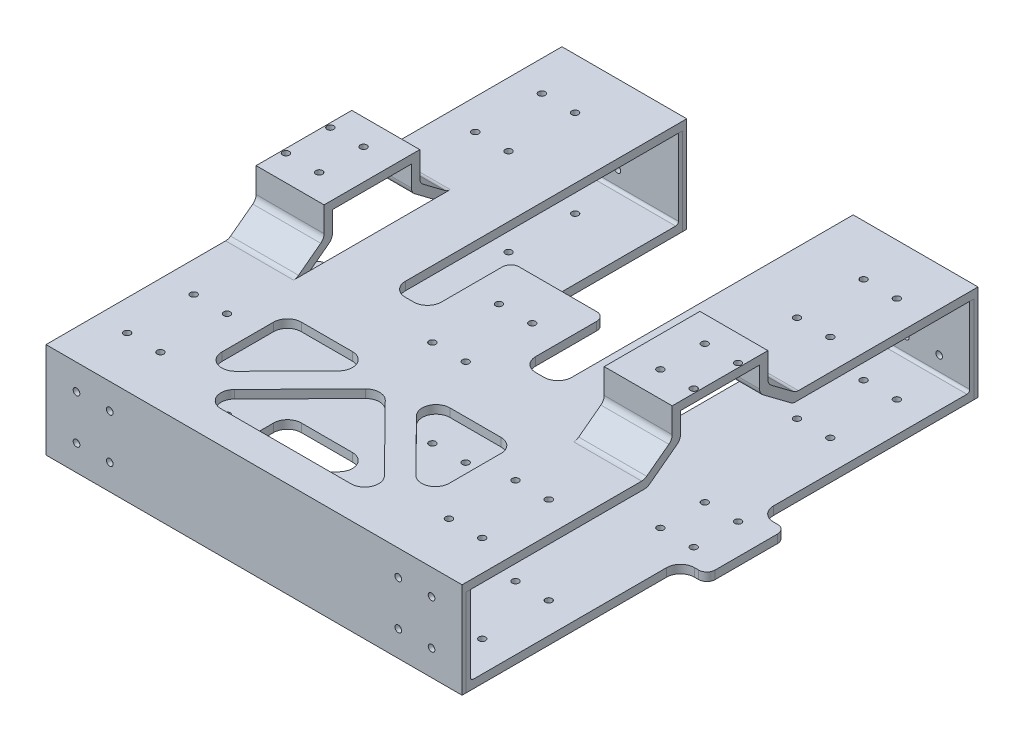
SolidWorks part; units mm, degrees
note: The reader was unsure of these and kept them because the rebuilt part matched: shared geometry of "Sketch14<6>".
ref_plane "Front" through (0, 0, 0) normal (0, 0, 1) x (1, 0, 0)
ref_plane "Top" through (0, 0, 0) normal (0, 1, 0) x (1, 0, 0)
ref_plane "Right" through (0, 0, 0) normal (1, 0, 0) x (0, 0, -1)
sketch "Top Layout" plane through (0, 0, 0) normal (0, 1, 0) x (1, 0, 0)
  line L0 (50.5, 0) -> (0, 0) construction
  line L5 (58, 43.5) -> (58, -43.5) construction
  line L6 (41, -78.75) -> (84, -78.75) construction
  line L25 (50.5, 0) -> (93.5, 0) construction
  line L26 (93.5, 50) -> (93.5, -50) construction
  line L27 (84, -28.75) -> (84, -128.75) construction
  line L31 (41, 78.75) -> (84, 78.75) construction
  line L32 (84, 128.75) -> (84, 28.75) construction
  point P0 (0, 0)
  point P6 (59.2, -42.4)
  point P8 (63.375, -50.8)
  point P9 (0, 0)
  point P16 (0, 0)
  point P24 (0, 0)
  point P25 (0, 0)
  point P26 (0, 0)
  line B0 (-6, -22.6978) -> (-6, 1.3022) construction
  line B1 (-17, -29.9478) -> (-17, 16.5522) construction
  line B2 (-17, -29.9478) -> (17, -29.9478) construction
  line B3 (17, -29.9478) -> (17, 16.5522) construction
  line B4 (-17, 16.5522) -> (17, 16.5522) construction
  line B5 (-6, 1.3022) -> (6, 1.3022) construction
  line B6 (6, 1.3022) -> (6, -22.6978) construction
  line B7 (6, -22.6978) -> (-6, -22.6978) construction
  line B8 (0, -22.6978) -> (0, -29.9478) construction
  line B9 (17, 5.3022) -> (-19, 5.3022) construction
  line B10 (75, -43.5) -> (41, -43.5) construction
  line B11 (75, -43.5) -> (75, -90) construction
  line B12 (75, -90) -> (41, -90) construction
  line B13 (41, -43.5) -> (41, -90) construction
  line B14 (58, -78.75) -> (58, -90) construction
  dimension "D2" = 75
  dimension "D5" = 90
  dimension "D7" = 9
  dimension "D8" = 100
  dimension "D9" = 90
  dimension "D10" = 9.5
sketch_block_instance "DYNAMIXEL 430 TopBot-1"
sketch_block "DYNAMIXEL 430 TopBot" parameters "D1"=28.5, "D2"=34, "D3"=20.267, "D4"=13.9544, "D5"=12.6443, "D6"=6.0635
sketch_block_instance "Flat 430 Block-1"
sketch_block "Flat 430 Block" parameters "D1"=46.5, "D2"=34, "D3"=11.25, "D4"=6.2771, "D5"=20.8671, "D6"=8.1058, "D7"=13.2568
sketch_block_instance "DYNAMIXEL 430 Side-1"
sketch_block "DYNAMIXEL 430 Side" parameters "D1"=34, "D2"=46.5, "D3"=12, "D4"=24, "D5"=11.25, "D6"=2, "D7"=4
sketch_block_instance "Block2-1"
sketch_block "Block2" parameters "D1"=12, "D2"=11, "D3"=4, "D4"=24, "D5"=13.103, "D6"=44.647, "D7"=34
sketch "Sketch3" plane through (0, 0, 0) normal (0, 1, 0) x (1, 0, 0)
  line L1 (-88.9, -102.9045) -> (88.9, -102.9045)
  line L2 (-88.9, -102.9045) -> (-88.9, 102.9045)
  line L3 (-88.9, 102.9045) -> (88.9, 102.9045)
  line L4 (88.9, -102.9045) -> (88.9, 102.9045)
  line L5 (-88.9, -102.9045) -> (88.9, 102.9045) construction
  line L6 (-88.9, 102.9045) -> (88.9, -102.9045) construction
  point P0 (0, 0)
sketch "Sketch4" plane through (0, 0, 0) normal (1, 0, 0) x (0, 0, -1)
  line L0 (-90, 28.5) -> (-90, 0)
  line L1 (-90, 0) -> (90, 0)
  line L2 (90, 0) -> (90, 28.5)
  line L3 (90, 28.5) -> (91.5, 28.5)
  line L4 (91.5, 28.5) -> (91.5, -3)
  line L5 (91.5, -3) -> (-91.5, -3)
  line L6 (-91.5, -3) -> (-91.5, 28.5)
  line L7 (-91.5, 28.5) -> (-90, 28.5)
  point P11 (0, 0)
  point P13 (0, 0)
  point P16 (88.9, 28.5)
  point P17 (-91.9, -3)
  point P18 (-91.9, 28.5)
  point P19 (-91.9, -3)
  point P20 (0, 0)
  line B0 (-90, 14.25) -> (-78.75, 14.25) construction
  line B1 (-43.5, 0) -> (-90, 0) construction
  line B2 (-43.5, 0) -> (-43.5, 28.5) construction
  line B3 (-43.5, 28.5) -> (-90, 28.5) construction
  line B4 (-90, 0) -> (-90, 28.5) construction
  line B5 (90, 14.25) -> (78.75, 14.25) construction
  line B6 (43.5, 28.5) -> (90, 28.5) construction
  line B7 (43.5, 28.5) -> (43.5, 0) construction
  line B8 (43.5, 0) -> (90, 0) construction
  line B9 (90, 28.5) -> (90, 0) construction
  dimension "D1" = 1.5
  dimension "D2" = 3
sketch_block_instance "DYNAMIXEL 430 Front-1"
sketch_block "DYNAMIXEL 430 Front" parameters "D1"=46.5, "D2"=28.5, "D3"=11.25, "D4"=8, "D5"=8, "D6"=11, "D7"=11
sketch_block_instance "DYNAMIXEL 430 Front-3"
extrude "Boss-Extrude1" add sketch "Sketch4" along direction (1, 0, 0) on the side of the normal up to vertex (84.5 mm away) contours L7 L6 L5 L4 L3 L2 L1 L0
ref_plane "Plane1" through (50.5, 0, 0) normal (1, 0, 0) x (0, 0, -1)
sketch "Sketch14" plane through (50.5, 0, 0) normal (1, 0, 0) x (0, 0, -1)
  line L0 (-91.5, -3) -> (-91.5, 28.5)
  line L1 (-91.5, 28.5) -> (-26.25, 28.5)
  line L2 (91.5, 28.5) -> (91.5, -3)
  line L3 (91.5, -3) -> (93, -3)
  line L4 (93, -3) -> (93, 31.5)
  line L5 (93, 31.5) -> (27.25, 31.5)
  line L6 (-93, 31.5) -> (-93, -3)
  line L7 (-93, -3) -> (-91.5, -3)
  line L9 (-17.25, 49.5) -> (17.25, 49.5)
  line L10 (-27.25, 31.5) -> (-93, 31.5)
  line L12 (-14.25, 46.5) -> (14.25, 46.5)
  line L13 (0, 50) -> (0, -50) construction
  line L16 (26.25, 28.5) -> (91.5, 28.5)
  line L17 (-27.25, 31.5) -> (27.25, 31.5)
  line L18 (-26.25, 28.5) -> (26.25, 28.5)
  line L19 (-14.25, 46.5) -> (-14.25, 37.5)
  line L20 (-14.25, 37.5) -> (-26.25, 28.5)
  line L21 (-27.25, 31.5) -> (-17.25, 39)
  line L22 (-17.25, 39) -> (-17.25, 49.5)
  line L23 (-14.25, 46.5) -> (-14.25, 49.5) construction
  line L24 (-14.25, 46.5) -> (-17.25, 46.5) construction
  line L25 (-22.2922, 35.2183) -> (-20.4922, 32.8183) construction
  line L26 (14.25, 46.5) -> (14.25, 37.5)
  line L27 (17.25, 39) -> (17.25, 49.5)
  line L28 (27.25, 31.5) -> (17.25, 39)
  line L29 (14.25, 37.5) -> (26.25, 28.5)
  point P10 (-17.6072, 39.8035)
  point P26 (-21.5122, 37.3791)
  point P30 (0, 46.5)
  point P31 (0, 49.5)
  point P35 (-28.2297, 31.5)
  line B0 (0, 0) -> (0, 11.25) construction
  line B1 (14.25, 46.5) -> (14.25, 0) construction
  line B2 (14.25, 46.5) -> (-14.25, 46.5) construction
  line B3 (-14.25, 46.5) -> (-14.25, 0) construction
  line B4 (14.25, 0) -> (-14.25, 0) construction
  dimension "D1" = 1.5
  dimension "D2" = 3
  dimension "D3" = 3
  dimension "D4" = 9
  dimension "D5" = 12
sketch_block_instance "DYNAMIXEL 430 Front-4"
sketch_block "DYNAMIXEL 430 Front" parameters "D1"=46.5, "D2"=28.5, "D3"=11.25, "D4"=8, "D5"=8, "D6"=11, "D7"=11
extrude "Boss-Extrude2" add sketch "Sketch14" along normal blind 34 separate body
sketch "Sketch7" plane through (0, -3, 0) normal (0, -1, 0) x (1, 0, 0)
  line L0 (84.5, -14.25) -> (75, -14.25)
  line L1 (50.5, -14.25) -> (84.5, -14.25) construction
  line L2 (75, -14.25) -> (75, -93)
  line L4 (75, -93) -> (84.5, -93)
  line L5 (84.5, -93) -> (84.5, -14.25)
  line L7 (84.5, 14.25) -> (75, 14.25)
  line L8 (84.5, 14.25) -> (84.5, 93)
  line L9 (84.5, 93) -> (75, 93)
  line L10 (75, 14.25) -> (75, 93)
  line L11 (75, -90) -> (75, -43.5) construction
  line L17 (0, -93) -> (30, -93)
  line L18 (30, -93) -> (30, 13.4478)
  line L19 (30, 13.4478) -> (17, 13.4478)
  line L20 (17, 29.9478) -> (17, -16.5522) construction
  line L21 (17, 13.4478) -> (17, -16.5522)
  line L22 (17, -16.5522) -> (0, -16.5522)
  line L23 (-17, -16.5522) -> (17, -16.5522) construction
  line L24 (0, -16.5522) -> (0, -93)
  line L25 (84.5, -93) -> (50.5, -93) construction
  line L26 (84.5, 93) -> (50.5, 93) construction
  line L27 (84.5, 93) -> (84.5, 91.5) construction
  dimension "D1" = 30
  dimension "D2" = 30
extrude "Boss-Extrude4" add sketch "Sketch14<6>" against normal up to surface (50.5 mm away) up to face at (0, 13.5, 0)
sketch "Sketch14<6>" plane through (50.5, 0, 0) normal (1, 0, 0) x (0, 0, -1) same geometry as "Sketch14"
extrude "Cut-Extrude1" cut sketch "Sketch7" against normal through all
sketch "Sketch16" plane through (0, 49.5, 0) normal (0, 1, 0) x (1, 0, 0)
  line L1 (84.5, 14.25) -> (75, 14.25)
  line L2 (84.5, 14.25) -> (84.5, -14.25)
  line L3 (84.5, -14.25) -> (75, -14.25)
  line L4 (75, 14.25) -> (75, -14.25)
extrude "Cut-Extrude2" cut sketch "Sketch16" against normal up to next (3 mm away)
hole_wizard "M2 Clearance Hole4" positions "Sketch12" profile "Sketch13" hole size "M2" standard "ANSI Metric" end condition through all
sketch "Sketch12" plane through (0, -3, 0) normal (0, 1, 0) x (1, 0, 0)
  point P0 (52, -74.75)
  point P3 (64, -74.75)
  point P6 (64, -50.75)
  point P9 (52, -50.75)
  point P12 (73.5, -8)
  point P15 (73.5, 8)
  point P18 (64, 74.75)
  point P21 (52, 74.75)
  point P24 (52, 50.75)
  point P27 (64, 50.75)
  point P30 (6, -22.6978)
  point P32 (6, 1.3022)
  point P34 (61.5, -8)
  point P36 (61.5, 8)
sketch "Sketch13" plane through (52, -3, 74.75) normal (1, 0, 0) x (0, 0, -1)
  line L0 (0, 0) -> (0, 52.5)
  line L1 (0, 52.5) -> (1.2, 52.5)
  line L2 (1.2, 52.5) -> (1.2, 0)
  line L5 (1.2, 0) -> (0, 0)
  line L11 (0, -6.35) -> (0, 107.95) construction
  dimension "Thru Hole Dia." = 2.4
  dimension "Thru Hole Depth" = 52.5
hole_wizard "M2 Clearance Hole5" positions "Sketch17" profile "Sketch18" hole size "M2" standard "ANSI Metric" end condition through all
sketch "Sketch17" plane through (0, 0, 93) normal (0, 0, 1) x (1, 0, 0)
  line L0 (41, 0) -> (84, 0) construction
  point P16 (52, 6.25)
  point P18 (64, 6.25)
  point P20 (64, 22.25)
  point P22 (52, 22.25)
  line B0 (41, 28.5) -> (75, 28.5) construction
sketch_block_instance "Block4-1"
sketch_block "Block4" parameters "D1"=28.5, "D2"=34, "D3"=20.267, "D4"=13.9544, "D5"=12.6443, "D6"=6.0635
sketch "Sketch18" plane through (52, 22.25, 93) normal (1, 0, 0) x (0, -1, 0)
  line L0 (0, 0) -> (0, 186)
  line L1 (0, 186) -> (1.2, 186)
  line L2 (1.2, 186) -> (1.2, 0)
  line L5 (1.2, 0) -> (0, 0)
  line L11 (0, -6.35) -> (0, 107.95) construction
  dimension "Thru Hole Dia." = 2.4
  dimension "Thru Hole Depth" = 186
mirror "Mirror1" about plane through (0, 0, 0) normal (1, 0, 0) of bodies 117 118 106 112
sketch "Sketch19" plane through (0, -3, 0) normal (0, -1, 0) x (1, 0, 0)
  line L0 (41, 43.5) -> (41, 90) construction
  line L1 (-41, 81.5) -> (41, 81.5)
  line L2 (-41, 81.5) -> (-41, 39.9478)
  line L3 (-41, 39.9478) -> (41, 39.9478)
  line L4 (41, 81.5) -> (41, 39.9478)
  line L5 (0, 0) -> (0, 81.5) construction
  line L6 (75, 91.5) -> (-75, 91.5) construction
  line L7 (-17, 29.9478) -> (17, 29.9478) construction
  line L8 (41, 81.5) -> (0, 39.9478) construction
  line L9 (0, 39.9478) -> (-41, 81.5) construction
  line L10 (38.1527, 84.3094) -> (0, 45.6429)
  line L11 (0, 45.6429) -> (-38.1527, 84.3094)
  line L12 (43.8473, 78.6906) -> (0, 34.2527)
  line L13 (0, 34.2527) -> (-43.8473, 78.6906)
  dimension "D1" = 10
  dimension "D2" = 10
  dimension "D3" = 4
  dimension "D4" = 4
extrude "Cut-Extrude3" cut sketch "Sketch19" against normal through all contours L4 L12 L3 | L11 L10 L1 | L3 L13 L2
fillet "Fillet1" radius 5 17 edges at (75, -1.5, 14.25) (75, -1.5, -14.25) (30, -1.5, 13.4478) (17, -1.5, 13.4478) (-17, -1.5, 13.4478) (-30, -1.5, 13.4478) (-75, -1.5, 14.25) (-75, -1.5, -14.25) (5.6194, -1.5, 39.9478) (41, -1.5, 75.8049) (41, -1.5, 39.9478) (0, -1.5, 45.6429) (-35.3806, -1.5, 81.5) (-41, -1.5, 39.9478) (-41, -1.5, 75.8049) (-5.6194, -1.5, 39.9478) (35.3806, -1.5, 81.5)
fillet "Fillet2" radius 3 5 edges at (-84.5, -1.5, -14.25) (-84.5, -1.5, 14.25) (84.5, -1.5, 14.25) (84.5, -1.5, -14.25) (-17, -1.5, -16.5522)
fillet "Fillet3" radius 1 3 edges at (-52.5, 0, -90) (52.5, 0, -90) (0, 0, 90)
fillet "Fillet5" radius 3 18 edges at (62.75, 28.5, -26.25) (62.75, 28.5, 26.25) (62.75, 31.5, 27.25) (62.75, 31.5, -27.25) (62.75, 39, 17.25) (62.75, 39, -17.25) (62.75, 37.5, -14.25) (62.75, 37.5, 14.25) (17, 30, -16.5522) (-62.75, 37.5, 14.25) (-62.75, 37.5, -14.25) (-62.75, 28.5, -26.25) (-62.75, 39, -17.25) (-62.75, 39, 17.25) (-62.75, 31.5, 27.25) (-62.75, 31.5, -27.25) (-62.75, 28.5, 26.25) (-17, 30, -16.5522)
fillet "Fillet7" radius 5 13 edges at (30, 30, 13.4478) (17, 30, 13.4478) (-30, 30, 13.4478) (-17, 30, 13.4478) (5.6194, 30, 39.9478) (41, 30, 75.8049) (35.3806, 30, 81.5) (0, 30, 45.6429) (-35.3806, 30, 81.5) (41, 30, 39.9478) (-41, 30, 39.9478) (-41, 30, 75.8049) (-5.6194, 30, 39.9478)
